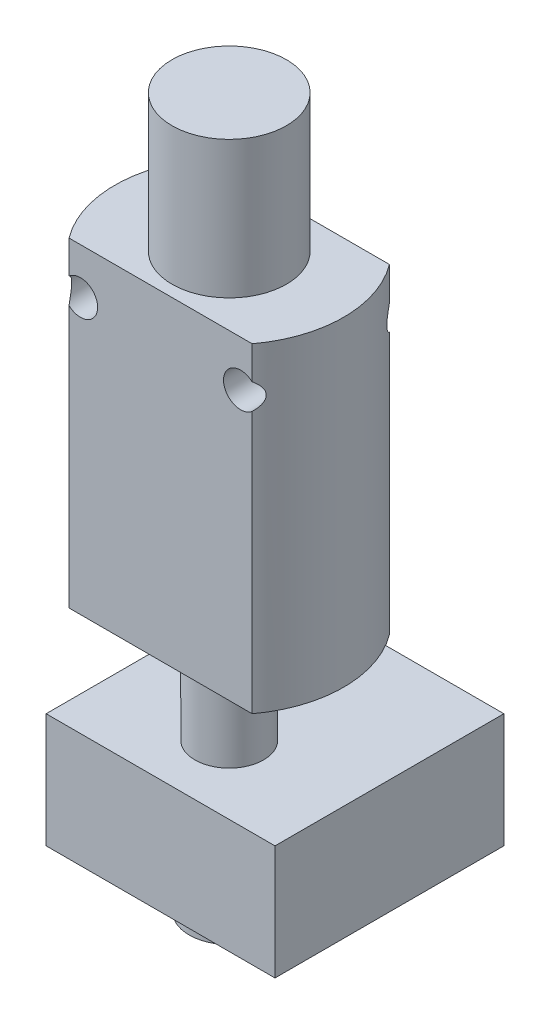
SolidWorks part; units mm, degrees
ref_plane "Plano frontal" through (0, 0, 0) normal (0, 0, 1) x (1, 0, 0)
ref_plane "Plano superior" through (0, 0, 0) normal (0, 1, 0) x (1, 0, 0)
ref_plane "Plano direito" through (0, 0, 0) normal (1, 0, 0) x (0, 0, -1)
sketch "Esboço1" plane through (0, 0, 0) normal (0, 0, 1) x (1, 0, 0)
  line L0 (0, 0) -> (0, 24.6707) construction
  line L2 (-10, 14) -> (10, 14)
  line L3 (-10, 14) -> (-10, -14)
  line L4 (-10, -14) -> (10, -14)
  line L5 (10, 14) -> (10, -14)
  line L6 (-10, 14) -> (10, -14) construction
  line L7 (-10, -14) -> (10, 14) construction
  circle A0 centre (-7, 10) radius 1.5
  circle A1 centre (7, 10) radius 1.5
  point P3 (0, 0)
  dimension "D4" = 3
  dimension "D1" = 28
  dimension "D2" = 20
  dimension "D3" = 14
  dimension "D5" = 4
extrude "Ressalto-extrusão1" add sketch "Esboço1" along normal mid plane 12
sketch "Esboço2" plane through (0, 0, 0) normal (0, 0, 1) x (1, 0, 0)
  line L0 (0, 0) -> (0, -38) construction
  line L1 (3, -33) -> (3, -23)
  line L3 (3, -33) -> (3.5, -33)
  line L4 (3.5, -33) -> (3.5, -36)
  line L5 (3.5, -36) -> (0.75, -38)
  line L6 (0.75, -38) -> (0, -38)
  line L7 (10, 14) -> (-10, 14) construction
  line L8 (3, -23) -> (3, -14)
  line L9 (-10, -14) -> (10, -14) construction
  line L10 (0, -38) -> (0, -14)
  line L11 (3, -14) -> (0, -14)
  line L12 (0, 26) -> (5, 26)
  line L13 (5, 26) -> (5, 14)
  line L14 (5, 14) -> (0, 14)
  line L15 (0, 26) -> (0, 14)
  dimension "D1" = 52
  dimension "D2" = 9
  dimension "D3" = 10
  dimension "D4" = 6
  dimension "D5" = 3
  dimension "D6" = 7
  dimension "D7" = 1.5
  dimension "D8" = 12
  dimension "D9" = 10
revolve "Revolução1" add sketch "Esboço2" angle 360 about L0
sketch "Esboço3" plane through (0, 0, 0) normal (0, 1, 0) x (1, 0, 0)
  line L0 (10, -6) -> (-10, -6) construction
  line L1 (-10, 14) -> (10, 14)
  line L2 (-10, 14) -> (-10, -6)
  line L3 (-10, -6) -> (10, -6)
  line L4 (10, 14) -> (10, -6)
  line L5 (-10, 14) -> (10, -6) construction
  line L6 (-10, -6) -> (10, 14) construction
  point P0 (0, 4)
  dimension "D1" = 20
extrude "Ressalto-extrusão2" add sketch "Esboço3" along normal blind 10 from surface starting at face at (-3, -33, 0)
sketch "Esboço4" plane through (0, 14, 0) normal (0, 1, 0) x (1, 0, 0)
  line L0 (-8, 6) -> (-10, 6)
  line L1 (8, -6) -> (10, -6)
  line L4 (10, 6) -> (-10, 6)
  line L5 (-10, 6) -> (-10, -6)
  line L6 (-10, -6) -> (10, -6)
  line L7 (10, -6) -> (10, 6)
  line L8 (10, 6) -> (8, 6)
  line L9 (-10, 6) -> (-10, -6)
  line L10 (-10, -6) -> (-8, -6)
  line L11 (10, -6) -> (10, 6)
  arc A0 (-8, 6) -> (-8, -6) centre (0, 0) ccw
  arc A1 (8, -6) -> (8, 6) centre (0, 0) ccw
  line M6 (10, 6) -> (-10, 6)
  line M7 (-10, 6) -> (-10, -6)
  line M8 (-10, -6) -> (10, -6)
  line M9 (10, -6) -> (10, 6)
  dimension "D1" = 0
extrude "Corte-extrusão1" cut sketch "Esboço4" against normal up to surface (28 mm away) contours A0 M6 M7 | A0 L9 M8 | A1 M8 M9 | A1 L11 M6 region at (-9.4119, 14, -4.5317) region at (9.4119, 14, -4.5317) region at (-9.4119, 14, 4.5317) region at (9.4119, 14, 4.5317) up to face at (-3, -14, 0)
